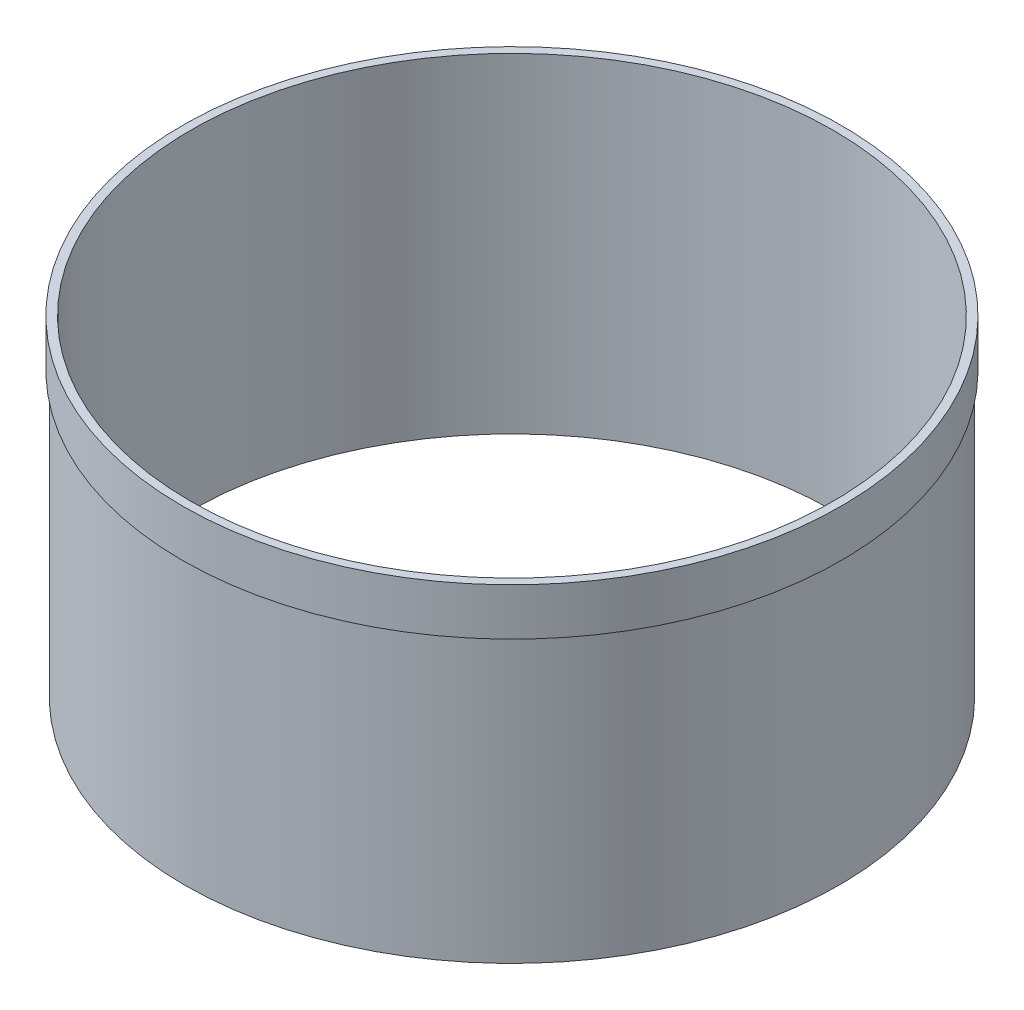
SolidWorks part; units mm, degrees
material "A-Glass Fiber"
ref_plane "Front Plane" through (0, 0, 0) normal (0, 0, 1) x (1, 0, 0)
ref_plane "Top Plane" through (0, 0, 0) normal (0, 1, 0) x (1, 0, 0)
ref_plane "Right Plane" through (0, 0, 0) normal (1, 0, 0) x (0, 0, -1)
sketch "Sketch1" plane through (0, 0, 0) normal (0, 1, 0) x (1, 0, 0)
  circle A0 centre (0, 0) radius 88.265
  circle A1 centre (0, 0) radius 86.6775
  dimension "D1" = 1.5875
  dimension "D2" = 176.53
extrude "Boss-Extrude1" add sketch "Sketch1" along normal blind 88.9
sketch "Sketch2" plane through (0, 88.9, 0) normal (0, 1, 0) x (1, 0, 0)
  circle A0 centre (0, 0) radius 88.265 construction
  circle A1 centre (0, 0) radius 88.265
  circle A2 centre (0, 0) radius 88.9
  dimension "D1" = 177.8
extrude "Boss-Extrude2" add sketch "Sketch2" against normal blind 12.7
